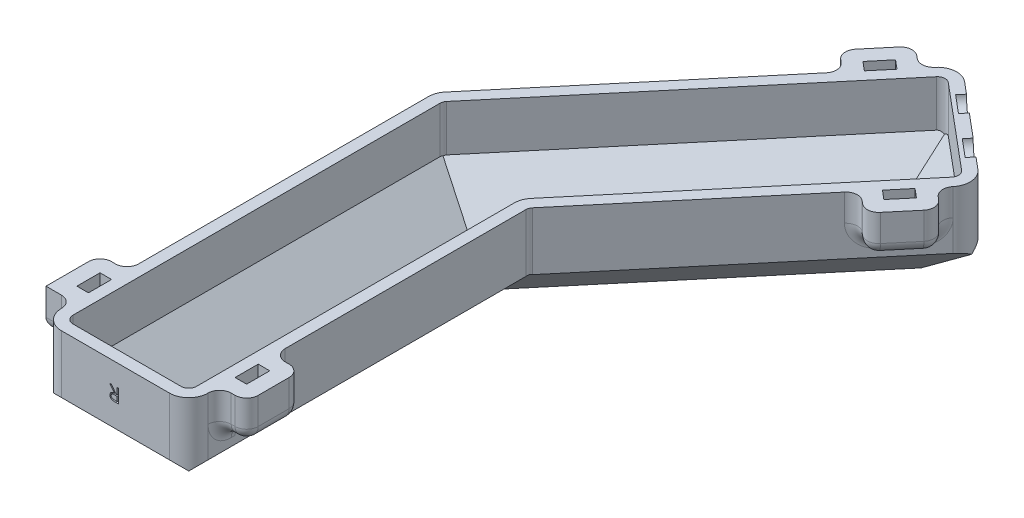
SolidWorks part; units mm, degrees
ref_plane "Front Plane" through (0, 0, 0) normal (0, 0, 1) x (1, 0, 0)
ref_plane "Top Plane" through (0, 0, 0) normal (0, 1, 0) x (1, 0, 0)
ref_plane "Right Plane" through (0, 0, 0) normal (1, 0, 0) x (0, 0, -1)
sketch "Sketch1" plane through (0, 0, 0) normal (0, 1, 0) x (1, 0, 0)
  line L0 (0, -95) -> (0, 0) construction
  line L1 (0, 0) -> (57.8509, 68.944) construction
  line L2 (19, -95) -> (19, -6.9154)
  line L3 (-19, -95) -> (-19, 6.9154)
  line L4 (-19, -95) -> (19, -95)
  line L5 (19, -6.9154) -> (72.4057, 56.731)
  line L6 (43.296, 81.157) -> (72.4057, 56.731)
  line L7 (43.296, 81.157) -> (-19, 6.9154)
  line L8 (43.6658, 76.9305) -> (68.1792, 56.3613) construction
  line L9 (43.6658, 76.9305) -> (-16, 5.8235) construction
  line L10 (-16, 5.8235) -> (-16, -92) construction
  line L11 (-16, -92) -> (16, -92) construction
  line L12 (16, -92) -> (16, -5.8235) construction
  line L13 (16, -5.8235) -> (68.1792, 56.3613) construction
  point P9 (0, -95)
  point P10 (57.8509, 68.944)
  point P12 (55.9225, 66.6459)
  point P13 (0, -92)
  dimension "D1" = 95
  dimension "D2" = 90
  dimension "D3" = 38
  dimension "D4" = 38
  dimension "D5" = 140
  dimension "D6" = 32
  dimension "D7" = 32
  dimension "D8" = 3
  dimension "D9" = 3
extrude "Boss-Extrude1" add sketch "Sketch1" along normal blind 25
sketch "Sketch2" plane through (0, 25, 0) normal (0, 1, 0) x (1, 0, 0)
  line L0 (43.6658, 76.9305) -> (68.1792, 56.3613)
  line L1 (43.6658, 76.9305) -> (-16, 5.8235)
  line L2 (-16, 5.8235) -> (-16, -92)
  line L3 (-16, -92) -> (16, -92)
  line L4 (16, -92) -> (16, -5.8235)
  line L5 (16, -5.8235) -> (68.1792, 56.3613)
  line L6 (0, 0) -> (57.8509, 68.944) construction
  line L7 (72.4057, 56.731) -> (43.296, 81.157) construction
  line L8 (0, 0) -> (0, -95) construction
  line L9 (-19, -95) -> (19, -95) construction
  point P0 (55.9225, 66.6459)
  point P1 (0, -92)
  dimension "D1" = 32
  dimension "D2" = 32
  dimension "D3" = 3
  dimension "D4" = 3
extrude "Cut-Extrude1" cut sketch "Sketch2" against normal blind 22
chamfer "Chamfer1" distance 10 angle 45 12 edges at (55.9225, 3, -66.6459) (42.0896, 3, -25.2689) (16, 3, 48.9118) (0, 3, 92) (-16, 3, 43.0882) (13.8329, 3, -41.377) (12.148, 0, -44.0362) (57.8509, 0, -68.944) (45.7029, 0, -24.9078) (19, 0, 50.9577) (-19, 0, 44.0423) (0, 0, 95)
fillet "Fillet1" radius 2 6 edges at (-16, 19, 92) (16, 19, 92) (-16, 19, -5.8235) (19, 17.5, 6.9154) (43.6658, 19, -76.9305) (68.1792, 19, -56.3613)
fillet "Fillet2" radius 5 6 edges at (-19, 17.5, 95) (19, 17.5, 95) (-19, 17.5, -6.9154) (16, 19, 5.8235) (72.4057, 17.5, -56.731) (43.296, 17.5, -81.157)
sketch "Sketch3" plane through (-14.5548, 0, -12.213) normal (-0.766, 0, -0.6428) x (-0.6428, 0, 0.766)
  line L0 (-85, 25) -> (5.0956, 25) construction
  line L1 (-68, 15) -> (-82, 15)
  line L2 (-68, 15) -> (-68, 25)
  line L3 (-68, 25) -> (-82, 25)
  line L4 (-82, 15) -> (-82, 25)
  line L5 (-68, 15) -> (-82, 25) construction
  line L6 (-68, 25) -> (-82, 15) construction
  line L7 (-85, 25) -> (-85, 10) construction
  point P0 (-75, 20)
  dimension "D1" = 10
  dimension "D2" = 14
  dimension "D3" = 3
sketch "Sketch4" plane through (14.5548, 0, 12.213) normal (0.766, 0, 0.6428) x (0.6428, 0, -0.766)
  line L0 (7.6434, 25) -> (85, 25) construction
  line L1 (82, 15) -> (68, 15)
  line L2 (82, 15) -> (82, 25)
  line L3 (82, 25) -> (68, 25)
  line L4 (68, 15) -> (68, 25)
  line L5 (82, 15) -> (68, 25) construction
  line L6 (82, 25) -> (68, 15) construction
  line L7 (85, 10) -> (85, 25) construction
  point P0 (75, 20)
  dimension "D1" = 3
  dimension "D2" = 10
  dimension "D3" = 14
sketch "Sketch6" plane through (-19, 0, 0) normal (-1, 0, 0) x (0, 0, 1)
  line L0 (-5.0956, 25) -> (90, 25) construction
  line L1 (87, 15) -> (73, 15)
  line L2 (87, 15) -> (87, 25)
  line L3 (87, 25) -> (73, 25)
  line L4 (73, 15) -> (73, 25)
  line L5 (87, 15) -> (73, 25) construction
  line L6 (87, 25) -> (73, 15) construction
  line L7 (90, 10) -> (90, 25) construction
  point P0 (80, 20)
  dimension "D1" = 3
  dimension "D2" = 14
  dimension "D3" = 10
sketch "Sketch7" plane through (19, 0, 0) normal (1, 0, 0) x (0, 0, -1)
  line L0 (-90, 25) -> (-7.6434, 25) construction
  line L1 (-73, 15) -> (-87, 15)
  line L2 (-73, 15) -> (-73, 25)
  line L3 (-73, 25) -> (-87, 25)
  line L4 (-87, 15) -> (-87, 25)
  line L5 (-73, 15) -> (-87, 25) construction
  line L6 (-73, 25) -> (-87, 15) construction
  line L7 (-90, 25) -> (-90, 10) construction
  point P0 (-80, 20)
  dimension "D1" = 10
  dimension "D2" = 14
  dimension "D3" = 3
sketch "Sketch9" plane through (0, 0, 95) normal (0, 0, 1) x (1, 0, 0)
  line L0 (0, 10) -> (0, 25) construction
  line L1 (-14, 10) -> (14, 10) construction
  line L2 (-14, 25) -> (14, 25) construction
  line L3 (14, 17.5) -> (-14, 17.5) construction
  line L4 (14, 10) -> (14, 25) construction
  line L5 (-14, 25) -> (-14, 10) construction
  text T0 "<r180>R</r>"
extrude "Cut-Extrude4" cut sketch "Sketch9" against normal blind 0.5
extrude "Boss-Extrude2" add sketch "Sketch3" along normal blind 7
extrude "Boss-Extrude3" add sketch "Sketch7" along normal blind 7
extrude "Boss-Extrude4" add sketch "Sketch6" along normal blind 7
extrude "Boss-Extrude5" add sketch "Sketch4" along normal blind 7
sketch "Sketch11" plane through (0, 25, 0) normal (0, 1, 0) x (1, 0, 0)
  line L0 (33.2845, 73.8928) -> (35.5826, 71.9644)
  line L1 (-22, -83) -> (-19, -83)
  line L2 (-22, -83) -> (-22, -77)
  line L3 (-22, -77) -> (-19, -77)
  line L4 (-19, -83) -> (-19, -77)
  line L5 (19, -77) -> (22, -77)
  line L6 (19, -77) -> (19, -83)
  line L7 (19, -83) -> (22, -83)
  line L8 (22, -77) -> (22, -83)
  line L9 (33.2845, 73.8928) -> (29.4277, 69.2965)
  line L10 (35.5826, 71.9644) -> (31.7259, 67.3682)
  line L11 (29.4277, 69.2965) -> (31.7259, 67.3682)
  line L12 (64.6923, 47.5385) -> (66.9904, 45.6101)
  line L13 (64.6923, 47.5385) -> (60.8356, 42.9422)
  line L14 (66.9904, 45.6101) -> (63.1337, 41.0139)
  line L15 (60.8356, 42.9422) -> (63.1337, 41.0139)
  line L16 (72.6257, 46.1032) -> (67.2634, 50.6027) construction
  line L17 (67.2634, 50.6027) -> (69.1918, 52.9008) construction
  line L18 (32.7914, 79.5281) -> (38.1537, 75.0286) construction
  line L19 (40.0821, 77.3267) -> (38.1537, 75.0286) construction
  line L21 (-19, 5.0956) -> (-19, -73) construction
  line L22 (19, -73) -> (19, -7.6434) construction
  line L23 (-26, -73) -> (-19, -73) construction
  dimension "D1" = 4
  dimension "D2" = 4
  dimension "D3" = 6
  dimension "D4" = 3
extrude "Cut-Extrude5" cut sketch "Sketch11" against normal through all
fillet "Fillet3" radius 3 35 edges at (-19, 20, 87) (-19, 20, 73) (19, 20, 87) (19, 20, 73) (58.2644, 20, -39.8781) (-22.5, 15, 87) (-19, 15, 85) (-26, 20, 73) (-26, 15, 80) (-19, 15, 75) (-22.5, 15, 73) (26, 20, 87) (22.5, 15, 87) (19, 15, 85) (19, 15, 75) (26, 15, 80) (26, 20, 73) (22.5, 15, 73) (63.6267, 20, -35.3785) (59.55, 15, -41.4101) (60.9456, 15, -37.6283) (68.1262, 15, -40.7409) (72.6257, 20, -46.1032) (69.9446, 15, -48.3529) (65.9779, 15, -49.0706) (67.2634, 20, -50.6027) (29.1547, 20, -64.304) (38.1537, 20, -75.0286) (30.4403, 15, -65.8361) (26.4736, 15, -66.5537) (23.7924, 20, -68.8035) (32.7914, 20, -79.5281) (28.2919, 15, -74.1658) (35.4726, 15, -77.2784) (36.8682, 15, -73.4965)
sketch "Sketch12" plane through (57.8509, 0, -68.944) normal (0.6428, 0, -0.766) x (-0.766, 0, -0.6428)
  line L0 (-14, 25) -> (14, 25) construction
  line L1 (0, 25) -> (0, 26.2737) construction
  circle A0 centre (7, 25) radius 3
  circle A1 centre (-7, 25) radius 3
  dimension "D1" = 6
  dimension "D2" = 7
extrude "Cut-Extrude6" cut sketch "Sketch12" against normal blind 2
